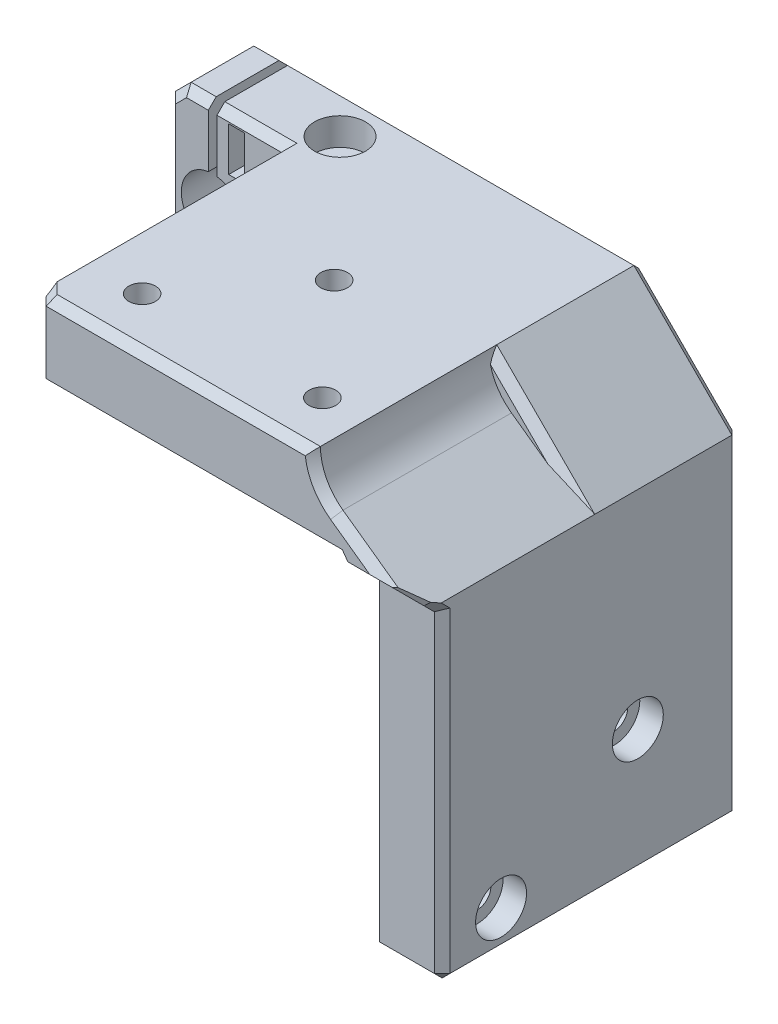
SolidWorks part; units mm, degrees
material "PET"
ref_plane "Front Plane" through (0, 0, 0) normal (0, 0, 1) x (1, 0, 0)
ref_plane "Top Plane" through (0, 0, 0) normal (0, 1, 0) x (1, 0, 0)
ref_plane "Right Plane" through (0, 0, 0) normal (1, 0, 0) x (0, 0, -1)
sketch "Sketch1" plane through (0, 0, -56) normal (0, 0, -1) x (-1, 0, 0)
  line L5 (-205.3, -20) -> (-205.3, -65)
  line L7 (-163.3, -20) -> (-205.3, -20)
  line L8 (-163.3, -20) -> (-163.3, -10)
  line L9 (-163.3, -10) -> (-214.3, -10)
  line L10 (-214.3, -65) -> (-214.3, -10)
  line L11 (-205.3, -65) -> (-214.3, -65)
  line L12 (-166.8, -10) -> (-158.3, -10) construction
  line L13 (-163.3, -20.5) -> (-163.3, -32) construction
  dimension "D1" = 10
  dimension "D2" = 9
  dimension "D3" = 55
extrude "Boss-Extrude1" add sketch "Sketch1" against normal up to surface (42 mm away)
sketch "Sketch19" plane through (0, 0, -56) normal (0, 0, -1) x (-1, 0, 0)
  line L0 (-201.8, -10) -> (-214.3, -22.5)
  line L2 (-214.3, -10) -> (-214.3, -65) construction
  line L3 (-214.3, -22.5) -> (-214.3, -10)
  line L4 (-214.3, -10) -> (-201.8, -10)
  line L8 (-163.3, -10) -> (-214.3, -10) construction
  line L10 (-201.8, -10) -> (-201.8, 4.4) construction
  line L11 (-166.8, -10) -> (-163.3, -13.5)
  line L12 (-166.8, -6.7416) -> (-166.8, -10) construction
  line L13 (-163.3, -20) -> (-163.3, -10) construction
  line L14 (-163.3, -13.5) -> (-163.3, -10)
  line L15 (-163.3, -10) -> (-166.8, -10)
extrude "Cut-Extrude7" cut sketch "Sketch19" against normal through all
sketch "Sketch17" plane through (214.3, 0, 0) normal (1, 0, 0) x (0, 0, -1)
  line L5 (14, -20) -> (18.0294, -24.0294)
  line L6 (18.0294, -24.0294) -> (18.0294, -69.25)
  line L8 (14, -69.25) -> (14, -20)
  line L24 (14, -65) -> (14, -22.5) construction
  line L26 (14, -69.25) -> (18.0294, -69.25)
  dimension "D1" = 45
extrude "Cut-Extrude5" cut sketch "Sketch17" against normal through all
hole_wizard "CBORE for M3 SHCS2" positions "Sketch3" profile "Sketch4" counterbore size "M3" standard "ANSI Metric" end condition through all
sketch "Sketch3" plane through (214.3, 0, 0) normal (1, 0, 0) x (0, 0, -1)
  point P0 (25.55, -60)
  point P3 (43, -49)
sketch "Sketch4" plane through (214.3, -60, -25.55) normal (0, 1, 0) x (0, 0, -1)
  line L0 (0, 0) -> (0, 51)
  line L1 (0, 51) -> (1.7, 51)
  line L3 (1.7, 51) -> (1.7, 3)
  line L4 (1.7, 3) -> (3.25, 3)
  line L5 (3.25, 3) -> (3.25, 0)
  line L7 (3.25, 0) -> (0, 0)
  line L11 (0, -6.35) -> (0, 107.95) construction
  dimension "Thru Hole Dia." = 3.4
  dimension "Thru Hole Depth" = 51
  dimension "C'Bore Dia." = 6.5
  dimension "C'Bore Depth" = 3
sketch "Sketch7" plane through (0, 0, -56) normal (0, 0, -1) x (-1, 0, 0)
  line L1 (-153.2, -28.75) -> (-155.2, -28.75) construction
  line L2 (-166.8, -10) -> (-163.3, -13.5)
  line L3 (-163.3, -13.5) -> (-163.3, -26.75)
  line L4 (-163.3, -26.75) -> (-161.3, -28.75)
  line L5 (-157.05, -21.75) -> (-157.05, -17.788) construction
  line L10 (-163.3, -10) -> (-163.3, -13.5) construction
  line L15 (-156.5, -17.788) -> (-157.6, -17.788) construction
  line L16 (-153.3, -28.75) -> (-151.3, -26.75)
  line L17 (-151.3, -12) -> (-153.3, -10)
  line L18 (-157.6, -10) -> (-166.8, -10)
  line L19 (-157.6, -17.788) -> (-157.6, -10)
  line L20 (-156.5, -10) -> (-156.5, -17.788)
  line L21 (-153.3, -10) -> (-156.5, -10)
  line L22 (-151.3, -26.75) -> (-151.3, -12)
  line L23 (-161.3, -28.75) -> (-153.3, -28.75)
  arc A1 (-156.5, -17.788) -> (-157.6, -17.788) centre (-157.05, -21.75) cw
  point P0 (-163.3, -28.75)
  dimension "D3" = 4
  dimension "D2" = 12
  dimension "D5" = 5.2
  dimension "D6" = 45
  dimension "D8" = 7
  dimension "D9" = 45
  dimension "D7" = 2
  dimension "D10" = 2
  dimension "D11" = 2
  dimension "D12" = 45
  dimension "D13" = 1.1
extrude "Boss-Extrude2" add sketch "Sketch7" against normal blind 10
hole_wizard "CBORE for M3 SHCS1" positions "Sketch8" profile "Sketch9" counterbore size "M3" standard "ANSI Metric"
sketch "Sketch8" plane through (151.3, 0, 0) normal (1, 0, 0) x (0, 0, -1)
  line L1 (51, -14) -> (51, -10) construction
  line L2 (46, -10) -> (56, -10) construction
  point P0 (51, -14)
  dimension "D1" = 4
sketch "Sketch9" plane through (151.3, -14, -51) normal (0, 1, 0) x (0, 0, 1)
  line L0 (0, 0) -> (0, 13.0215)
  line L1 (0, 13.0215) -> (1.7, 12)
  line L2 (1.7, 12) -> (1.7, 3)
  line L3 (1.7, 3) -> (3.25, 3)
  line L4 (3.25, 3) -> (3.25, 0)
  line L5 (3.25, 0) -> (0, 0)
  line L10 (0, 13.0215) -> (-1.7, 12) construction
  line L11 (0, -6.35) -> (0, 107.95) construction
  dimension "Hole Dia." = 3.4
  dimension "Hole Depth" = 12
  dimension "C'Bore Dia." = 6.5
  dimension "C'Bore Depth" = 3
  dimension "Drill Angle" = 118
sketch "Sketch10" plane through (0, 0, -46) normal (0, 0, 1) x (1, 0, 0)
  line L1 (161.1, -11.2) -> (159.1, -11.2)
  line L2 (161.1, -11.2) -> (161.1, -16.8)
  line L3 (161.1, -16.8) -> (159.1, -16.8)
  line L4 (159.1, -11.2) -> (159.1, -16.8)
  line L5 (157.6, -10) -> (166.8, -10) construction
  line L6 (154.3, -14) -> (159.1, -14) construction
  line L7 (154.3, -10.75) -> (154.3, -17.25) construction
  line L8 (160.1, -11.2) -> (160.1, -10) construction
  line L10 (157.6, -17.788) -> (157.6, -10) construction
  dimension "D1" = 5.6
  dimension "D2" = 2
  dimension "D3" = 1.5
extrude "Cut-Extrude3" cut sketch "Sketch10" against normal blind 8
chamfer "Chamfer14" distance 4.5 angle 45 1 edges at (163.3, -16.75, -14)
sketch "Sketch11" plane through (0, -20, 0) normal (0, -1, 0) x (1, 0, 0)
  line L1 (185.9166, -31.45) -> (182.6834, -31.45)
  line L2 (182.6834, -31.45) -> (181.0668, -34.25)
  line L3 (181.0668, -34.25) -> (182.6834, -37.05)
  line L4 (182.6834, -37.05) -> (185.9166, -37.05)
  line L5 (185.9166, -37.05) -> (187.5332, -34.25)
  line L6 (187.5332, -34.25) -> (185.9166, -31.45)
  line L7 (175.1666, -23.3) -> (176.7832, -20.5)
  line L8 (176.7832, -20.5) -> (175.1666, -17.7)
  line L9 (175.1666, -17.7) -> (171.9334, -17.7)
  line L10 (171.9334, -17.7) -> (170.3168, -20.5)
  line L11 (170.3168, -20.5) -> (171.9334, -23.3)
  line L12 (171.9334, -23.3) -> (175.1666, -23.3)
  line L13 (194.9334, -23.3) -> (198.1666, -23.3)
  line L14 (198.1666, -23.3) -> (199.7832, -20.5)
  line L15 (199.7832, -20.5) -> (198.1666, -17.7)
  line L16 (198.1666, -17.7) -> (194.9334, -17.7)
  line L17 (194.9334, -17.7) -> (193.3168, -20.5)
  line L18 (193.3168, -20.5) -> (194.9334, -23.3)
  circle A0 centre (184.3, -34.25) radius 2.8 construction
  circle A1 centre (173.55, -20.5) radius 2.8 construction
  circle A2 centre (196.55, -20.5) radius 2.8 construction
  dimension "D1" = 5.6
extrude "Cut-Extrude4" cut sketch "Sketch11" against normal blind 5
hole_wizard "M3 Clearance Hole2" positions "Sketch13" profile "Sketch14" hole size "M3" standard "ANSI Metric" end condition through all
sketch "Sketch13" plane through (0, -15, 0) normal (0, -1, 0) x (-1, 0, 0)
  point P0 (-184.3, 34.25)
  point P3 (-196.55, 20.5)
  point P5 (-173.55, 20.5)
sketch "Sketch14" plane through (184.3, -15, -34.25) normal (1, 0, 0) x (0, 0, -1)
  line L0 (0, 0) -> (0, 5)
  line L1 (0, 5) -> (1.7, 5)
  line L2 (1.7, 5) -> (1.7, 0)
  line L5 (1.7, 0) -> (0, 0)
  line L11 (0, -6.35) -> (0, 107.95) construction
  dimension "Thru Hole Dia." = 3.4
  dimension "Thru Hole Depth" = 5
chamfer "Chamfer3" distance 1 angle 45 1 edges at (205.3, -22.0147, -16.0147)
chamfer "Chamfer1" distance 1 angle 45 34 edges at (214.3, -43.75, -56) (214.3, -65, -37.0147) (184.3, -20, -56) (205.3, -42.5, -56) (205.3, -65, -37.0147) (163.3, -20, -32.25) (165.55, -20, -16.25) (187.05, -20, -14) (205.3, -43.8076, -18.0294) (214.3, -44.5147, -18.0294) (214.3, -23.2647, -17.2647) (162.2, -10, -46) (157.6, -14, -49.3) (154.9, -10, -46) (152.3, -11, -46) (151.3, -19.375, -46) (152.3, -27.75, -46) (157.3, -28.75, -46) (152.3, -11, -56) (151.3, -19.375, -56) (152.3, -27.75, -56) (157.3, -28.75, -56) (209.8, -65, -18.0294) (209.8, -65, -56) (213.05, -21.25, -15.25) (206.8, -15, -14) (208.05, -16.25, -56) (163.3, -23.375, -56) (162.3, -27.75, -46) (162.3, -27.75, -56) (179.7, -10, -56) (154.9, -10, -56) (167.3, -10, -14.5) (184.8, -10, -14)
sketch "Sketch18" plane through (0, 0, -36.5) normal (0, 0, 1) x (1, 0, 0)
  line L0 (163.3, -10) -> (167.8, -10) construction
  line L1 (166.8, -10) -> (166.8, -4.4) construction
  line L5 (201.8, -4.6) -> (201.8, -10) construction
  line L8 (201.8, -10) -> (214.3, -10)
  line L9 (214.3, -10) -> (214.3, -22.5)
  line L10 (204.6771, -15.6023) -> (214.3, -22.5)
  line L12 (166.8, -10) -> (163.3, -10)
  line L13 (157.6, -10) -> (166.8, -10) construction
  line L14 (163.3, -10) -> (163.3, -16)
  line L15 (163.3, -19) -> (163.3, -13.5) construction
  arc A0 (166.8, -10) -> (163.3, -16) centre (159.9071, -10) cw
  arc A1 (201.8, -10) -> (204.6771, -15.6023) centre (208.6929, -10) ccw
  dimension "D1" = 6
extrude "Cut-Extrude6" cut sketch "Sketch18" along normal through all
chamfer "Chamfer15" distance 1 angle 45 6 edges at (206.9917, -17.2613, -14) (202.9723, -13.8453, -14) (163.3, -14.75, -36.5) (163.3, -22.6679, -46) (165.05, -11.75, -36.5) (208.05, -16.25, -36.5)
hole_wizard "Tap Drill for M3x0.5 Tap1" positions "Sketch22" profile "Sketch23" hole size "M3x0.5" standard "ANSI Metric"
sketch "Sketch22" plane through (0, -65, 0) normal (0, -1, 0) x (-1, 0, 0)
  point P0 (-209.85, 23.1314)
sketch "Sketch23" plane through (209.85, -65, -23.1314) normal (1, 0, 0) x (0, 0, -1)
  line L0 (0, 0) -> (0, 3.7511)
  line L1 (0, 3.7511) -> (1.25, 3)
  line L2 (1.25, 3) -> (1.25, 0)
  line L5 (1.25, 0) -> (0, 0)
  line L10 (0, 3.7511) -> (-1.25, 3) construction
  line L11 (0, -6.35) -> (0, 107.95) construction
  dimension "Hole Dia." = 2.5
  dimension "Hole Depth" = 3
  dimension "Drill Angle" = 118
pattern_linear "LPattern1" count 7 spacing 4.5614 along (0, 0, -1) of "Tap Drill for M3x0.5 Tap1"
hole_wizard "CBORE for M3 SHCS3" positions "Sketch25" profile "Sketch26" counterbore size "M3" standard "ANSI Metric" end condition through all
sketch "Sketch25" plane through (0, -10, 0) normal (0, 1, 0) x (1, 0, 0)
  point P0 (168.8, 50.5)
sketch "Sketch26" plane through (168.8, -10, -50.5) normal (1, 0, 0) x (0, 0, 1)
  line L0 (0, 0) -> (0, 55)
  line L1 (0, 55) -> (1.7, 55)
  line L3 (1.7, 55) -> (1.7, 3.5)
  line L4 (1.7, 3.5) -> (3.25, 3.5)
  line L5 (3.25, 3.5) -> (3.25, 0)
  line L7 (3.25, 0) -> (0, 0)
  line L11 (0, -6.35) -> (0, 107.95) construction
  dimension "Thru Hole Dia." = 3.4
  dimension "Thru Hole Depth" = 55
  dimension "C'Bore Dia." = 6.5
  dimension "C'Bore Depth" = 3.5
equation "\"D9@Sketch7\"=\"D6@Sketch7\""
equation "\"D10@Sketch7\"=\"D7@Sketch7\""
